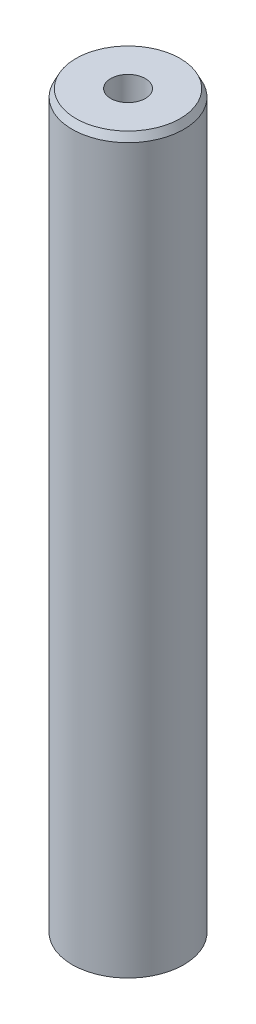
SolidWorks part; units mm, degrees
ref_plane "Front Plane" through (0, 0, 0) normal (0, 0, 1) x (1, 0, 0)
ref_plane "Top Plane" through (0, 0, 0) normal (0, 1, 0) x (1, 0, 0)
ref_plane "Right Plane" through (0, 0, 0) normal (1, 0, 0) x (0, 0, -1)
sketch "Sketch1" plane through (0, 0, 0) normal (0, 1, 0) x (1, 0, 0)
  circle A0 centre (0, 0) radius 5
  dimension "SHAFT_OD" = 10
extrude "Boss-Extrude1" add sketch "Sketch1" along normal blind 65.7822
sketch "Sketch2" plane through (0, 0, 0) normal (0, 1, 0) x (1, 0, 0)
  circle A0 centre (0, 0) radius 1.5496
  dimension "BORE_D" = 3.0992
extrude "Cut-Extrude1" cut sketch "Sketch2" along normal through all
chamfer "Chamfer1" distance 0.6674 angle 26.489 2 edges at (0, 65.7822, 5) (0, 0, 5) first distance on face at (0, 65.7822, 5) first distance on face at (0, 0, 1.5496)
